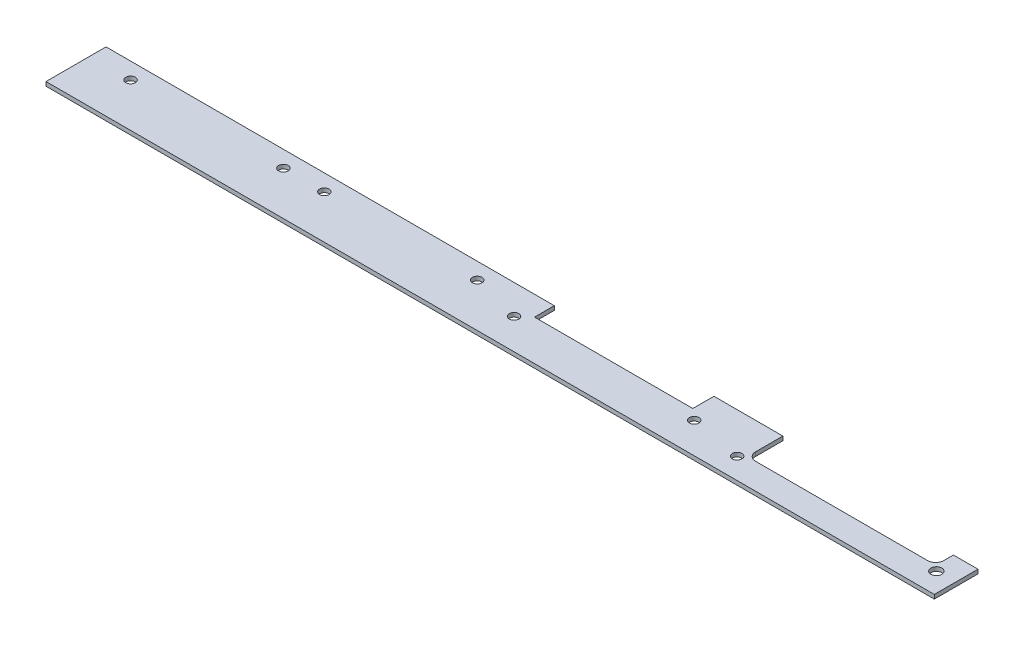
SolidWorks part; units mm, degrees
material "Простая углеродистая сталь"
ref_plane "Спереди" through (0, 0, 0) normal (0, 0, 1) x (1, 0, 0)
ref_plane "Сверху" through (0, 0, 0) normal (0, 1, 0) x (1, 0, 0)
ref_plane "Справа" through (0, 0, 0) normal (1, 0, 0) x (0, 0, -1)
sketch "Эскиз1" plane through (0, 0, 0) normal (0, 1, 0) x (1, 0, 0)
  line L0 (247.5, 22.5) -> (247.5, 12.5)
  line L1 (0, 0) -> (325.5, 0)
  line L2 (0, 0) -> (0, 22)
  line L5 (250.5, 9.5) -> (313.5, 9.5)
  line L7 (316.5, 12.5) -> (316.5, 16)
  line L8 (316.5, 16) -> (325.5, 16)
  line L9 (325.5, 16) -> (325.5, 0)
  line L10 (142, 11.25) -> (232.3, 11.25) construction
  line L11 (0, 22) -> (164.25, 22)
  line L12 (164.25, 22) -> (164.25, 14.75)
  line L14 (247.5, 22.5) -> (222.25, 22.5)
  line L15 (222.25, 22.5) -> (222.25, 14.75)
  line L16 (222.25, 14.75) -> (164.25, 14.75)
  line L17 (239.9138, 7.75) -> (323.1796, 7.75) construction
  circle A1 centre (245.5, 7.75) radius 1.75
  circle A2 centre (71, 16) radius 1.75
  circle A3 centre (15, 16) radius 1.75
  circle A4 centre (86, 16) radius 1.75
  circle A5 centre (142, 16) radius 1.75
  circle A8 centre (318.5, 7.75) radius 2
  arc A9 (247.5, 12.5) -> (250.5, 9.5) centre (250.5, 12.5) ccw
  arc A10 (313.5, 9.5) -> (316.5, 12.5) centre (313.5, 12.5) ccw
  circle A11 centre (160.25, 11.25) radius 1.75
  circle A12 centre (226.25, 11.25) radius 1.75
  point P31 (0, 0)
  dimension "D2" = 3
  dimension "D3" = 3
  dimension "D4" = 4
  dimension "D1" = 4
  dimension "D5" = 11.25
  dimension "D6" = 7.75
extrude "Бобышка-Вытянуть1" add sketch "Эскиз1" along normal blind 1.5
